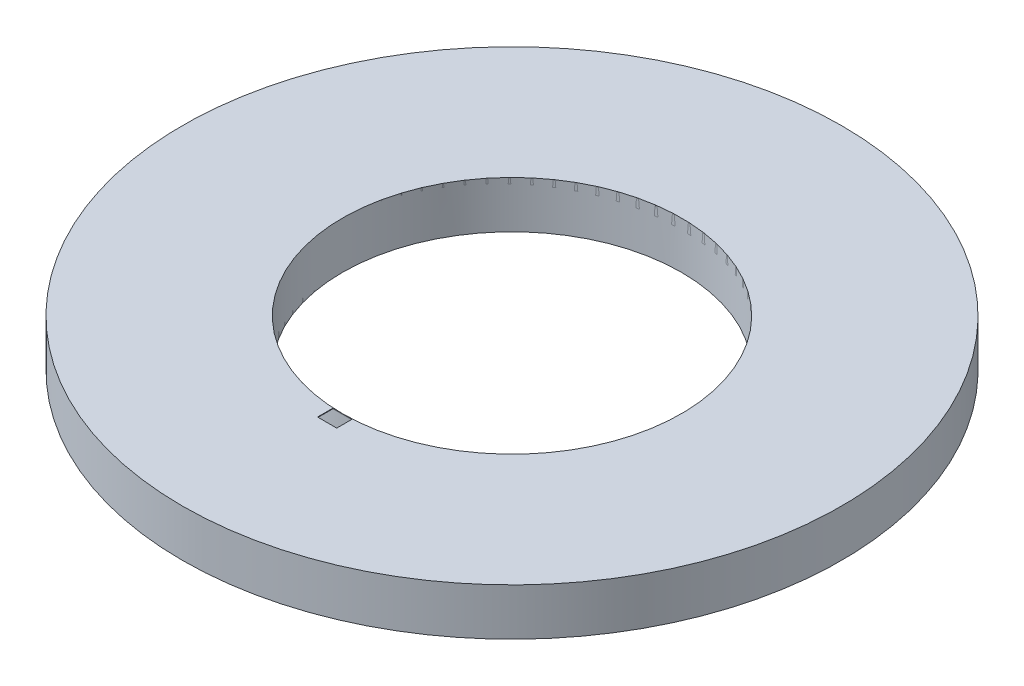
SolidWorks part; units mm, degrees
material "1345 Alloy"
ref_plane "Front Plane" through (0, 0, 0) normal (0, 0, 1) x (1, 0, 0)
ref_plane "Top Plane" through (0, 0, 0) normal (0, 1, 0) x (1, 0, 0)
ref_plane "Right Plane" through (0, 0, 0) normal (1, 0, 0) x (0, 0, -1)
sketch "Sketch1" plane through (0, 0, 0) normal (0, 1, 0) x (1, 0, 0)
  circle A0 centre (0, 0) radius 1750
extrude "Boss-Extrude1" add sketch "Sketch1" along normal blind 500
sketch "Sketch2" plane through (0, 500, 0) normal (0, 1, 0) x (1, 0, 0)
  circle A0 centre (0, 0) radius 900
extrude "Cut-Extrude2" cut sketch "Sketch2" against normal blind 300
sketch "Sketch3" plane through (0, 0, 0) normal (0, -1, 0) x (1, 0, 0)
  circle A0 centre (0, 0) radius 600
extrude "Cut-Extrude3" cut sketch "Sketch3" against normal blind 300
sketch "Sketch4" plane through (0, 0, 0) normal (0, -1, 0) x (-1, 0, 0)
  circle A0 centre (0, 0) radius 900.75
  circle A1 centre (0, 0) radius 1748.5
extrude "Cut-Extrude5" cut sketch "Sketch4" against normal blind 497
sketch "Sketch5" plane through (0, 0, 0) normal (0, 0, 1) x (1, 0, 0)
  line L0 (0, 0) -> (0, 250)
  line L1 (0, 250) -> (1750, 250)
  line L2 (1750, 0) -> (1750, 500) construction
  line L3 (1750, 250) -> (1750, 0)
  line L4 (1750, 0) -> (-1750, 0)
  line L5 (-1750, 0) -> (-1750, 250)
  line L6 (-1750, 500) -> (-1750, 0) construction
  line L7 (-1750, 250) -> (0, 250)
extrude "Cut-Extrude6" cut sketch "Sketch5" against normal through all both and the other way through all contours L7 L5 L4 L0 | L4 L3 L1 L0 region at (-875, 125, 0) region at (875, 125, 0)
sketch "Sketch6" plane through (0, 497, 0) normal (0, -1, 0) x (1, 0, 0)
  line L0 (0, 900.75) -> (51, 900.75)
  line L1 (51, 900.75) -> (51, 981.75)
  line L2 (51, 981.75) -> (-51, 981.75)
  line L3 (-51, 981.75) -> (-51, 900.75)
  line L4 (-51, 900.75) -> (0, 900.75)
  circle A0 centre (0, 0) radius 900.75 construction
  circle A1 centre (0, 0) radius 900.75 construction
extrude "Cut-Extrude7" cut sketch "Sketch6" against normal blind 10
